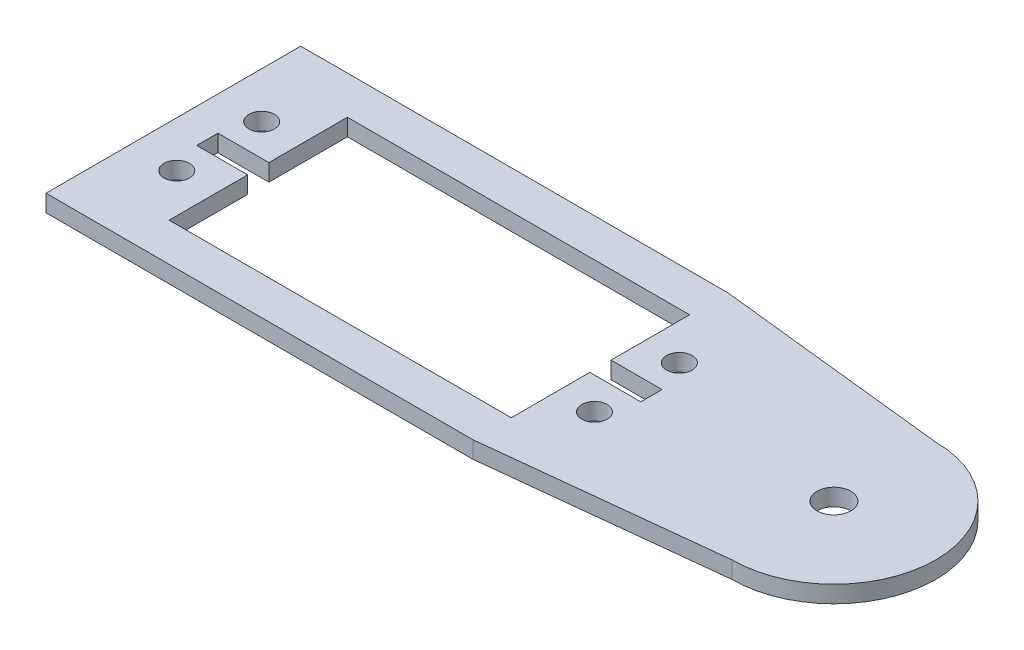
SolidWorks part; units mm, degrees
ref_plane "Спереди" through (0, 0, 0) normal (0, 0, 1) x (1, 0, 0)
ref_plane "Сверху" through (0, 0, 0) normal (0, 1, 0) x (1, 0, 0)
ref_plane "Справа" through (0, 0, 0) normal (1, 0, 0) x (0, 0, -1)
sketch "Эскиз1" plane through (0, 0, 0) normal (0, 1, 0) x (1, 0, 0)
  line L0 (5.4, -5) -> (5.4, 5) construction
  line L5 (10, 10.5) -> (50.3, 10.5)
  line L6 (10, 10.5) -> (10, -10.5) construction
  line L7 (10, -10.5) -> (50.3, -10.5)
  line L8 (5.4, -5) -> (54.6, -5) construction
  line L9 (54.6, -5) -> (54.6, 5) construction
  line L11 (5.4, 5) -> (54.6, 5) construction
  line L18 (50.3, 10.5) -> (50.3, -10.5)
  line L21 (10, -10.5) -> (10, 10.5)
  line L24 (0, 15) -> (50.3, 15)
  line L25 (50.3, 15) -> (77.8, 12)
  line L26 (0, 15) -> (0, -15)
  line L27 (0, -15) -> (50.3, -15)
  line L28 (50.3, -15) -> (77.8, -12)
  line L29 (0, 0) -> (89.8, 0) construction
  circle A0 centre (5.4, -5) radius 1.5
  circle A1 centre (5.4, 5) radius 1.5
  circle A2 centre (54.6, -5) radius 1.5
  circle A3 centre (54.6, 5) radius 1.5
  circle A4 centre (77.8, 0) radius 2
  arc A6 (77.8, -12) -> (77.8, 12) centre (77.8, 0) ccw
  point P1 (5.4, 0)
  point P2 (10, 0)
  dimension "D6" = 3
  dimension "D9" = 10
  dimension "D10" = 49.2
  dimension "D13" = 4
  dimension "D15" = 12
  dimension "D2" = 30
  dimension "D3" = 40.3
  dimension "D4" = 21
  dimension "D5" = 4.6
  dimension "D7" = 10
  dimension "D16" = 77.8
  dimension "D18" = 50.3
extrude "Основа" add sketch "Эскиз1" along normal blind 2
sketch "Sketch1" plane through (0, 2, 0) normal (0, 1, 0) x (1, 0, 0)
  line L0 (10, 0) -> (50.3, 0) construction
  line L1 (50.3, -10.5) -> (50.3, 10.5) construction
  line L2 (10, 10.5) -> (10, -10.5) construction
  line L3 (4, 1.25) -> (10, 1.25)
  line L4 (4, 1.25) -> (4, -1.25)
  line L5 (4, -1.25) -> (10, -1.25)
  line L6 (10, 1.25) -> (10, -1.25)
  line L7 (30.15, 10.5) -> (30.15, -10.5) construction
  line L8 (50.3, 10.5) -> (10, 10.5) construction
  line L9 (10, -10.5) -> (50.3, -10.5) construction
  line L10 (56.3, -1.25) -> (50.3, -1.25)
  line L11 (50.3, 1.25) -> (50.3, -1.25)
  line L12 (56.3, 1.25) -> (50.3, 1.25)
  line L13 (56.3, 1.25) -> (56.3, -1.25)
  point P17 (10.8569, 0)
  point P18 (10, 0.0835)
  dimension "D1" = 6
  dimension "D2" = 2.5
extrude "Вырезы под уголки жесткости на серве" cut sketch "Sketch1" against normal up to next
